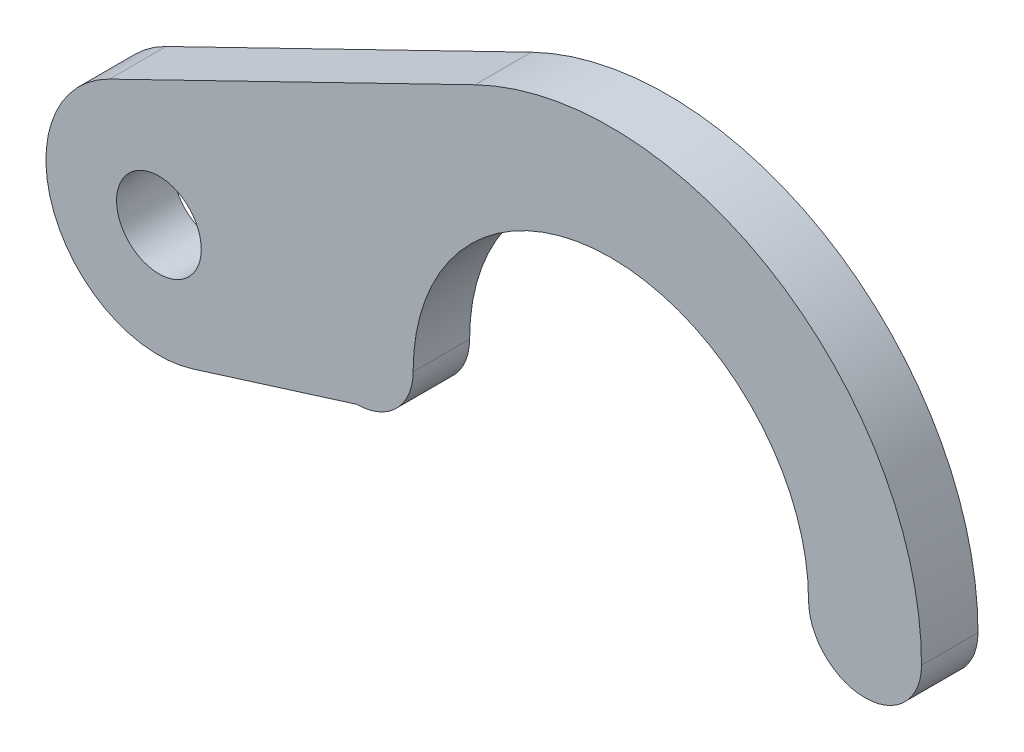
SolidWorks part; units mm, degrees
material "Acrylic (Medium-high impact)"
ref_plane "Front" through (0, 0, 0) normal (0, 0, 1) x (1, 0, 0)
ref_plane "Top" through (0, 0, 0) normal (0, 1, 0) x (1, 0, 0)
ref_plane "Right" through (0, 0, 0) normal (1, 0, 0) x (0, 0, -1)
sketch "Sketch1" plane through (0, 0, 0) normal (0, 0, 1) x (1, 0, 0)
  circle A0 centre (0, 0) radius 25.4
  dimension "D1" = 50.8
sketch "Sketch2" plane through (0, 0, 0) normal (0, 0, 1) x (1, 0, 0)
  line L0 (0, 0) -> (-93.9046, 0) construction
  line L1 (-56.3562, 11.4201) -> (-15.2797, 31.4052)
  line L2 (-47.0057, -12.12) -> (-28.575, -6.35)
  line L3 (0, 0) -> (100.627, 0) construction
  circle A0 centre (-50.8, 0) radius 4.7625
  arc A1 (-56.3562, 11.4201) -> (-47.0057, -12.12) centre (-50.8, 0) ccw
  arc A2 (22.225, 0) -> (-22.225, 0) centre (0, 0) ccw
  arc A3 (34.925, 0) -> (-15.2797, 31.4052) centre (0, 0) ccw
  arc A7 (22.225, 0) -> (34.925, 0) centre (28.575, 0) ccw
  arc A8 (-28.575, -6.35) -> (-22.225, 0) centre (-28.575, 0) ccw
  point P15 (0, 0)
  point P18 (-28.575, -6.35)
  dimension "D1" = 9.525
  dimension "D2" = 25.4
  dimension "D3" = 44.45
  dimension "D4" = 69.85
  dimension "D5" = 50.8
extrude "Boss-Extrude1" add sketch "Sketch2" along normal blind 6.35
